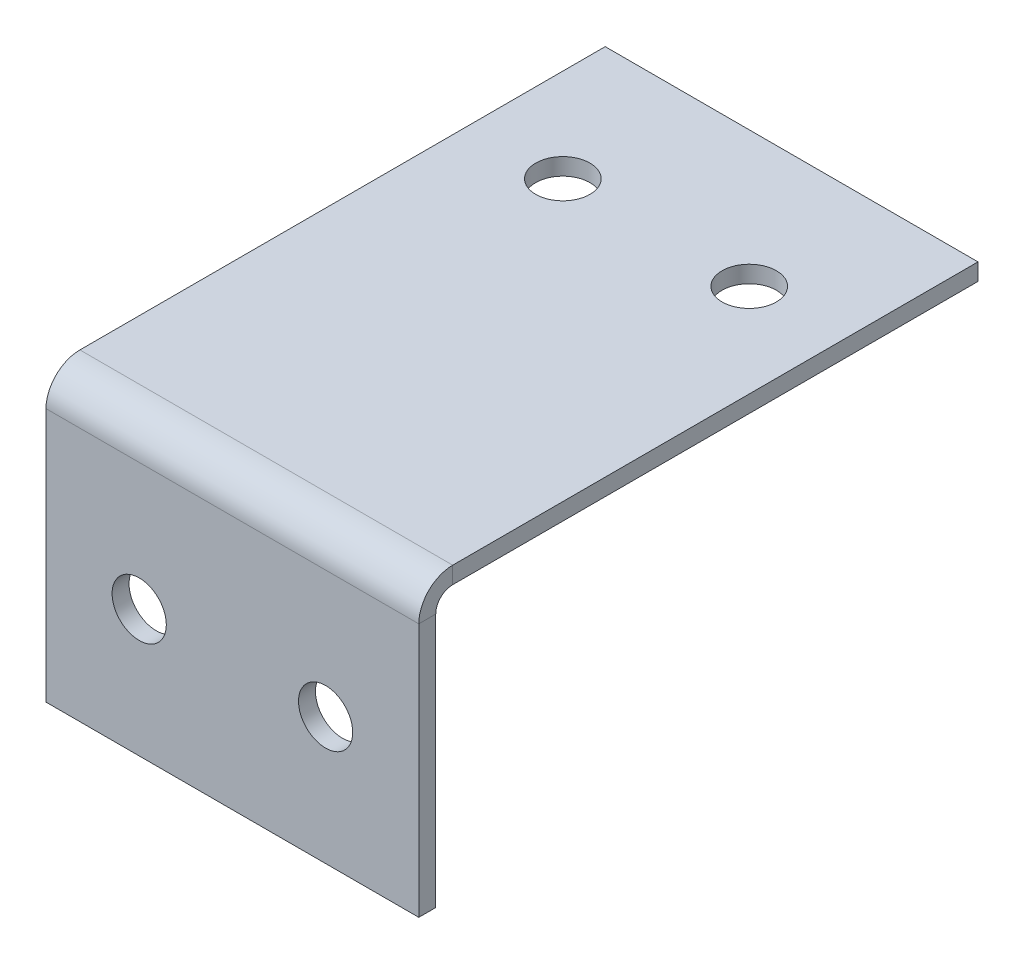
SolidWorks part; units mm, degrees
note: The reader was unsure of these and kept them because the rebuilt part matched: bend radius of "BaseBend1".
ref_plane "Front Plane" through (0, 0, 0) normal (0, 0, 1) x (1, 0, 0)
ref_plane "Top Plane" through (0, 0, 0) normal (0, 1, 0) x (1, 0, 0)
ref_plane "Right Plane" through (0, 0, 0) normal (1, 0, 0) x (0, 0, -1)
sketch "Sketch1" plane through (0, 0, 0) normal (1, 0, 0) x (0, 0, -1)
  line L0 (0, 0) -> (0, 25.4)
  line L1 (0, 25.4) -> (50.8, 25.4)
  dimension "D1" = 25.4
  dimension "D2" = 50.8
base flange "Base-Flange1" sketch "Sketch1" end condition mid plane depth 34.925 reverse direction yes thickness 1.5875 reverse thickness direction yes bend radius 1.5875
bend "BaseBend1" bend radius 1.5875 bend angle 90 parameters "D5"=1
sketch "Sketch6" plane through (0, 0, 1.5875) normal (0, 0, 1) x (1, 0, 0)
  line L0 (-17.4625, 11.9062) -> (17.4625, 11.9062) construction
  line L1 (-17.4625, 0) -> (-17.4625, 23.8125) construction
  line L2 (17.4625, 0) -> (17.4625, 23.8125) construction
  line L3 (-17.4625, 23.8125) -> (-8.7312, 11.9062) construction
  line L4 (-8.7312, 11.9062) -> (0, 23.8125) construction
  line L5 (-17.4625, 23.8125) -> (17.4625, 23.8125) construction
  line L6 (0, 23.8125) -> (8.7312, 11.9062) construction
  line L7 (8.7312, 11.9062) -> (17.4625, 23.8125) construction
  line L8 (-8.7312, 11.9062) -> (0, 0) construction
  line L9 (-17.4625, 0) -> (17.4625, 0) construction
  line L10 (0, 0) -> (8.7312, 11.9062) construction
  circle A0 centre (-8.7312, 11.9062) radius 2.54
  circle A1 centre (8.7312, 11.9062) radius 2.54
  dimension "D1" = 5.08
extrude "Cut-Extrude1" cut sketch "Sketch6" against normal blind 2.54
sketch "Sketch7" plane through (0, 26.9875, 0) normal (0, 1, 0) x (1, 0, 0)
  line L0 (-17.4625, 38.1) -> (17.4625, 38.1) construction
  line L4 (-17.4625, 1.5875) -> (-17.4625, 50.8) construction
  line L5 (17.4625, 1.5875) -> (17.4625, 50.8) construction
  line L6 (-17.4625, 50.8) -> (17.4625, 50.8) construction
  line L7 (-8.7312, 38.1) -> (0, 50.8) construction
  line L8 (0, 50.8) -> (8.7312, 38.1) construction
  line L9 (8.7312, 38.1) -> (17.4625, 50.8) construction
  circle A0 centre (-8.7312, 38.1) radius 2.54
  circle A1 centre (8.7312, 38.1) radius 2.54
  dimension "D2" = 12.7
  dimension "D1" = 5.08
extrude "Cut-Extrude2" cut sketch "Sketch7" against normal blind 2.54
sketch "Bend-Lines1" [suppressed] plane through (0, 0, 0) normal (0, 1, 0) x (1, 0, 0)
sketch "Bounding-Box1" [suppressed] plane through (0, 0, 0) normal (0, 1, 0) x (1, 0, 0)
sheet metal parameters "Sheet-Metal2" thickness 1.5875 parameters "D1"=1.5875
flat pattern "Flat-Pattern2" [suppressed]
sketch "Bend-Lines2" plane through (0, 26.9875, 0) normal (0, 1, 0) x (1, 0, 0)
  line L0 (18.2562, -0.2827) -> (-18.2562, -0.2827) construction
  line L1 (18.2562, -0.2827) -> (-18.2562, -0.2827) construction
sketch3d "Bounding-Box2" [suppressed]
  line L0 (0, -25.9655, 0) -> (0, 50.8, 0) construction
  line L1 (36.5125, -25.9655, 0) -> (36.5125, 50.8, 0) construction
  line L2 (0, -25.9655, 0) -> (36.5125, -25.9655, 0) construction
  line L3 (0, 50.8, 0) -> (36.5125, 50.8, 0) construction
bend of the flat pattern "Flatten-<BaseBend1>1"
sheet metal parameters "Sheet-Metal3" thickness 1.5875 parameters "D1"=1.5875
flat pattern "Flat-Pattern2"
sketch "Bend-Lines2" plane through (0, 26.9875, 0) normal (0, 1, 0) x (1, 0, 0)
  line L0 (18.2562, -0.2827) -> (-18.2563, -0.2827) construction
  line L1 (18.2562, -0.2827) -> (-18.2563, -0.2827) construction
sketch3d "Bounding-Box2" [suppressed]
  line L0 (0, -25.9655, 0) -> (0, 50.8, 0) construction
  line L1 (36.5125, -25.9655, 0) -> (36.5125, 50.8, 0) construction
  line L2 (0, -25.9655, 0) -> (36.5125, -25.9655, 0) construction
  line L3 (0, 50.8, 0) -> (36.5125, 50.8, 0) construction
bend of the flat pattern "Flatten-<BaseBend1>1"
sheet metal parameters "Sheet-Metal4" thickness 1.5875 parameters "D1"=1.5875
flat pattern "Flat-Pattern2"
sketch "Bend-Lines2" plane through (0, 26.9875, 0) normal (0, 1, 0) x (1, 0, 0)
  line L0 (17.4625, -0.2827) -> (-17.4625, -0.2827) construction
  line L1 (17.4625, -0.2827) -> (-17.4625, -0.2827) construction
sketch3d "Bounding-Box2" [suppressed]
  line L0 (0, -25.9655, 0) -> (0, 50.8, 0) construction
  line L1 (34.925, -25.9655, 0) -> (34.925, 50.8, 0) construction
  line L2 (0, -25.9655, 0) -> (34.925, -25.9655, 0) construction
  line L3 (0, 50.8, 0) -> (34.925, 50.8, 0) construction
bend of the flat pattern "Flatten-<BaseBend1>1"
